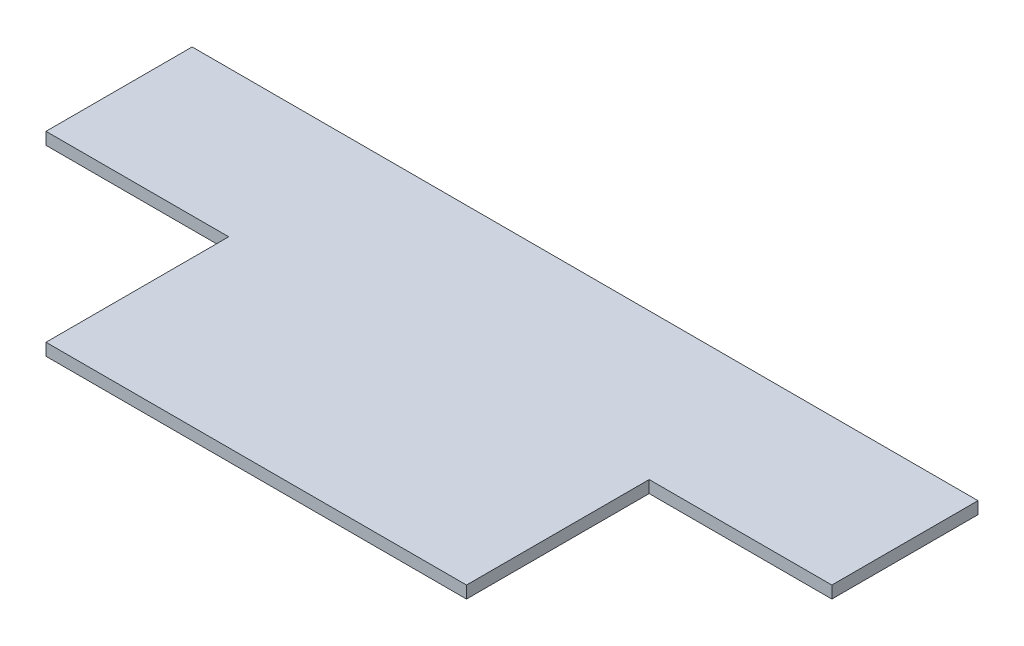
SolidWorks part; units mm, degrees
material "5052-H32"
ref_plane "Front Plane" through (0, 0, 0) normal (0, 0, 1) x (1, 0, 0)
ref_plane "Top Plane" through (0, 0, 0) normal (0, 1, 0) x (1, 0, 0)
ref_plane "Right Plane" through (0, 0, 0) normal (1, 0, 0) x (0, 0, -1)
sketch "Sketch1" plane through (0, 0, 0) normal (0, 1, 0) x (1, 0, 0)
  line L0 (0, 0) -> (102.4382, 0)
  line L1 (102.4382, 0) -> (102.4382, -19.05)
  line L2 (102.4382, -19.05) -> (78.6257, -19.05)
  line L3 (78.6257, -19.05) -> (78.6257, -42.8625)
  line L4 (78.6257, -42.8625) -> (23.8125, -42.8625)
  line L5 (23.8125, -42.8625) -> (23.8125, -19.05)
  line L6 (23.8125, -19.05) -> (0, -19.05)
  line L7 (0, -19.05) -> (0, 0)
  line L8 (23.8125, -19.05) -> (23.8125, 0) construction
  line L9 (78.6257, -19.05) -> (78.6257, 0) construction
  line L10 (23.8125, -19.05) -> (78.6257, -19.05) construction
  dimension "D1" = 54.8132
  dimension "D2" = 23.8125
  dimension "D3" = 23.8125
  dimension "D4" = 19.05
base flange "Base-Flange2" sketch "Sketch1" thickness 1.5875 reverse thickness direction no parameters "D1"=0.7366
sketch "Bend-Lines3" [suppressed] plane through (0, 0, 0) normal (0, 1, 0) x (1, 0, 0)
sketch "Bounding-Box3" [suppressed] plane through (0, 0, 0) normal (0, 1, 0) x (1, 0, 0)
sheet metal parameters "Sheet-Metal2" thickness 1.5875 parameters "D1"=0.7366
flat pattern "Flat-Pattern2" [suppressed]
sketch "Bend-Lines4" plane through (0, 0, 0) normal (0, 1, 0) x (1, 0, 0)
sketch3d "Bounding-Box4" [suppressed]
  line L0 (102.4382, 0, 0) -> (0, 0, 0) construction
  line L1 (102.4382, -42.8625, 0) -> (0, -42.8625, 0) construction
  line L2 (102.4382, 0, 0) -> (102.4382, -42.8625, 0) construction
  line L3 (0, 0, 0) -> (0, -42.8625, 0) construction
